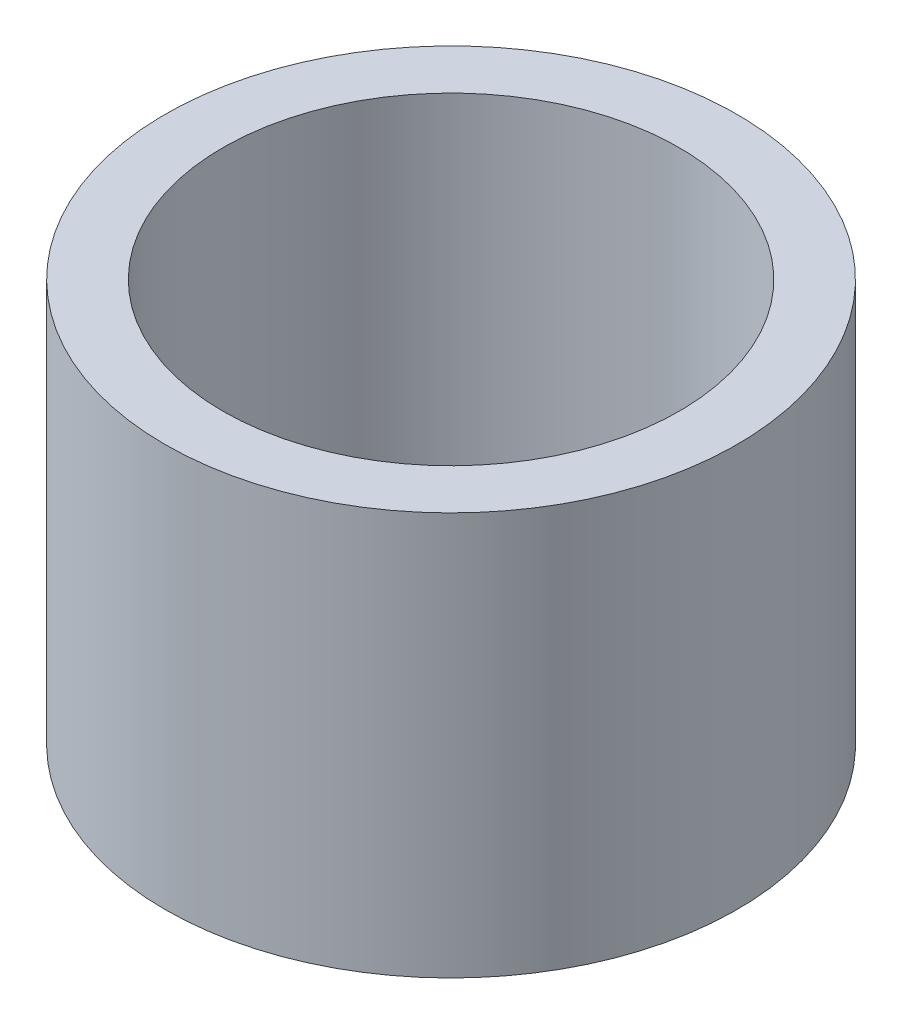
SolidWorks part; units mm, degrees
ref_plane "Front Plane" through (0, 0, 0) normal (0, 0, 1) x (1, 0, 0)
ref_plane "Top Plane" through (0, 0, 0) normal (0, 1, 0) x (1, 0, 0)
ref_plane "Right Plane" through (0, 0, 0) normal (1, 0, 0) x (0, 0, -1)
ref_axis "Axial" through (0, 3.81, 0) along (0, -1, 0)
ref_plane "Bottom Plane" through (0, -76.2, 0) normal (0, 1, 0) x (1, 0, 0)
sketch "Sketch1" plane through (0, 0, 0) normal (0, 1, 0) x (1, 0, 0)
  circle A0 centre (0, 0) radius 43.18
  circle A1 centre (0, 0) radius 54.102
  dimension "D1" = 108.204
  dimension "D2" = 86.36
extrude "Ablative" add sketch "Sketch1" against normal blind 76.2
